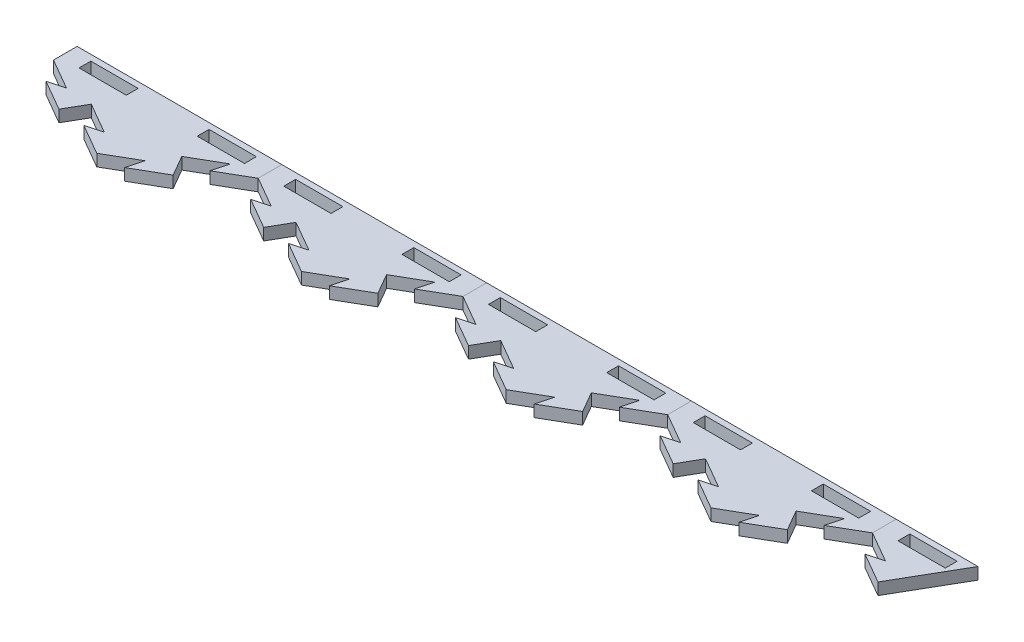
SolidWorks part; units mm, degrees
material "Cedar"
ref_plane "Front Plane" through (0, 0, 0) normal (0, 0, 1) x (1, 0, 0)
ref_plane "Top Plane" through (0, 0, 0) normal (0, 1, 0) x (1, 0, 0)
ref_plane "Right Plane" through (0, 0, 0) normal (1, 0, 0) x (0, 0, -1)
sketch "Sketch1" plane through (0, 0, 0) normal (0, 1, 0) x (1, 0, 0)
  line L0 (-54.9926, 0) -> (54.9926, 0) construction
  line L1 (-54.9926, 0) -> (0, -31.75)
  line L2 (0, -31.75) -> (54.9926, 0)
  line L3 (54.9926, 0) -> (54.9926, 63.5)
  line L4 (54.9926, 63.5) -> (0, 95.25)
  line L5 (0, 95.25) -> (-54.9926, 63.5)
  line L6 (-54.9926, 63.5) -> (-54.9926, 0)
  line L7 (0, -31.75) -> (0, 31.75) construction
  circle A0 centre (0, 31.75) radius 54.9926 construction
  point P9 (0, 0)
  dimension "D1" = 63.5
extrude "Boss-Extrude1" add sketch "Sketch1" against normal blind 6.35
sketch "Sketch2" plane through (0, 0, 0) normal (0, 1, 0) x (1, 0, 0)
  line L0 (-54.9926, 31.75) -> (54.9926, 31.75) construction
  line L1 (-54.9926, 63.5) -> (-54.9926, 0) construction
  line L2 (54.9926, 0) -> (54.9926, 63.5) construction
  point P2 (0, 31.75)
ref_axis "Axis1" through (0, 0, -31.75) along (0, 1, 0)
sketch "Sketch10" plane through (0, 0, 0) normal (0, 1, 0) x (1, 0, 0)
  line L0 (0, -31.75) -> (-16.4978, -22.225) construction
  line L1 (-16.4978, -22.225) -> (-7.8235, -19.9007)
  line L2 (-7.8235, -19.9007) -> (-24.3213, -10.3757)
  line L3 (-24.3213, -10.3757) -> (-27.4963, -15.875)
  line L4 (-16.4978, -22.225) -> (-27.4963, -15.875)
  line L5 (-54.9926, 0) -> (0, -31.75) construction
  dimension "D1" = 45
  dimension "D2" = 6.35
extrude "Cut-Extrude4" cut sketch "Sketch10" against normal through all
sketch "Sketch11" plane through (0, 0, 0) normal (0, 1, 0) x (1, 0, 0)
  line L0 (-27.4963, -15.875) -> (-54.9926, 0) construction
  line L1 (-27.4963, -15.875) -> (-30.6713, -21.3743)
  line L2 (-30.6713, -21.3743) -> (-47.1691, -11.8493)
  line L3 (-47.1691, -11.8493) -> (-38.4948, -9.525)
  line L4 (-38.4948, -9.525) -> (-27.4963, -15.875)
  line L5 (-38.4948, -9.525) -> (-54.9926, 0) construction
  line L6 (-38.4948, -9.525) -> (-54.9926, 0) construction
  line L7 (-54.9926, 0) -> (-27.4963, -15.875) construction
  line L8 (-54.9926, 63.5) -> (-54.9926, 0) construction
  dimension "D1" = 45
  dimension "D2" = 6.35
extrude "Boss-Extrude4" add sketch "Sketch11" against normal blind 6.35
pattern_circular "CirPattern1" count 2 every 60 about axis through (0, 0, -31.75) along (0, 1, 0) of "Cut-Extrude4", "Boss-Extrude4"
sketch "Sketch12" plane through (0, 0, 0) normal (0, 1, 0) x (1, 0, 0)
  line L0 (-54.9926, 12.7) -> (54.9926, 12.7)
  line L1 (-54.9926, 63.5) -> (-54.9926, 0) construction
  line L2 (54.9926, 0) -> (54.9926, 63.5) construction
  line L3 (54.9926, 12.7) -> (54.9926, 95.25)
  line L4 (54.9926, 95.25) -> (-54.9926, 95.25)
  line L5 (-54.9926, 95.25) -> (-54.9926, 12.7)
  line L6 (0, 0) -> (0, 12.7) construction
  dimension "D1" = 12.7
extrude "Cut-Extrude5" cut sketch "Sketch12" against normal through all
sketch "Sketch13" plane through (0, 0, 0) normal (0, 1, 0) x (1, 0, 0)
  line L0 (0, 0) -> (0, 12.7) construction
  line L1 (-54.9926, 12.7) -> (54.9926, 12.7) construction
  line L2 (-31.75, 6.35) -> (31.75, 6.35) construction
  line L4 (-44.45, 9.525) -> (-19.05, 9.525)
  line L5 (-44.45, 9.525) -> (-44.45, 3.175)
  line L6 (-44.45, 3.175) -> (-19.05, 3.175)
  line L7 (-19.05, 9.525) -> (-19.05, 3.175)
  line L8 (-44.45, 9.525) -> (-19.05, 3.175) construction
  line L9 (-44.45, 3.175) -> (-19.05, 9.525) construction
  line L10 (19.05, 9.525) -> (44.45, 9.525)
  line L11 (19.05, 9.525) -> (19.05, 3.175)
  line L12 (19.05, 3.175) -> (44.45, 3.175)
  line L13 (44.45, 9.525) -> (44.45, 3.175)
  line L14 (19.05, 9.525) -> (44.45, 3.175) construction
  line L15 (19.05, 3.175) -> (44.45, 9.525) construction
  point P7 (0, 6.35)
  point P8 (0, 6.35)
  dimension "D1" = 6.35
  dimension "D2" = 25.4
  dimension "D3" = 6.35
  dimension "D4" = 25.4
  dimension "D5" = 63.5
extrude "Cut-Extrude6" cut sketch "Sketch13" against normal through all
pattern_linear "LPattern1" count 5 spacing 109.9852 along (1, 0, 0) count 2 spacing 109.9852 along (-1, 0, 0) pattern seed only yes of bodies 136 131
sketch "Sketch14" plane through (0, 0, 0) normal (0, 1, 0) x (1, 0, 0)
  line L0 (439.9409, -31.75) -> (439.9409, 12.7)
  line L1 (384.9483, 12.7) -> (494.9335, 12.7) construction
  line L2 (439.9409, 12.7) -> (494.9335, 12.7)
  line L3 (494.9335, 12.7) -> (494.9335, -31.75)
  line L4 (494.9335, -31.75) -> (439.9409, -31.75)
  line L5 (-109.9852, -31.75) -> (-109.9852, 12.7)
  line L6 (-164.9778, 12.7) -> (-54.9926, 12.7) construction
  line L7 (-109.9852, 12.7) -> (-164.9778, 12.7)
  line L8 (-164.9778, 12.7) -> (-164.9778, -31.75)
  line L9 (-164.9778, -31.75) -> (-109.9852, -31.75)
  line L10 (415.6196, -10.3757) -> (428.9424, 12.7)
  line L11 (428.9424, 12.7) -> (439.9409, 12.7)
  line L12 (415.6196, -10.3757) -> (409.2696, -21.3743)
  line L13 (409.2696, -21.3743) -> (439.9409, -31.75)
  line L14 (-79.3139, -21.3743) -> (-98.9867, 12.7)
  line L15 (-98.9867, 12.7) -> (-109.9852, 12.7)
  line L16 (-79.3139, -21.3743) -> (-95.8117, -30.8993)
  line L17 (-95.8117, -30.8993) -> (-109.9852, -31.75)
  line L18 (-85.6639, -10.3757) -> (-79.3139, -21.3743) construction
  line M5 (484.3909, 9.525) -> (484.3909, 3.175)
  line M6 (484.3909, 3.175) -> (458.9909, 3.175)
  line M7 (458.9909, 3.175) -> (458.9909, 9.525)
  line M8 (458.9909, 9.525) -> (484.3909, 9.525)
  line M13 (494.9335, 12.7) -> (384.9483, 12.7)
  line M19 (415.6196, -10.3757) -> (432.1174, -19.9007)
  line M20 (432.1174, -19.9007) -> (423.4431, -22.225)
  line M21 (423.4431, -22.225) -> (439.9409, -31.75)
  line M22 (439.9409, -31.75) -> (456.4387, -22.225)
  line M23 (456.4387, -22.225) -> (454.1144, -30.8993)
  line M24 (454.1144, -30.8993) -> (470.6122, -21.3743)
  line M25 (470.6122, -21.3743) -> (464.2622, -10.3757)
  line M26 (464.2622, -10.3757) -> (480.76, -0.8507)
  line M27 (480.76, -0.8507) -> (478.4357, -9.525)
  line M28 (478.4357, -9.525) -> (494.9335, 0)
  line M29 (494.9335, 0) -> (494.9335, 12.7)
extrude "Cut-Extrude7" cut sketch "Sketch14" against normal through all contours L17 L16 L14 L15 L5 | L10 L0 M19 M20 M21 M13 | L0 M22 M23 M24 M25 M26 M27 M28 M29 M13 M8 M5 M6 M7 | L8 L9 L5 L7 region at (431.3731, 0, 7.3494) region at (460.5225, 0, 5.1278) region at (-137.4815, 0, 9.525) region at (-98.715, 0, 11.4335)
sketch "Sketch15" plane through (0, 0, 0) normal (0, 1, 0) x (1, 0, 0)
  line L0 (-98.9867, 12.7) -> (-54.9926, 12.7)
  line L1 (-54.9926, 12.7) -> (-54.9926, -10.3757)
  line L2 (-54.9926, -10.3757) -> (-98.9867, -10.3757)
  line L3 (-98.9867, -10.3757) -> (-98.9867, 12.7)
extrude "Cut-Extrude8" cut sketch "Sketch15" against normal through all
